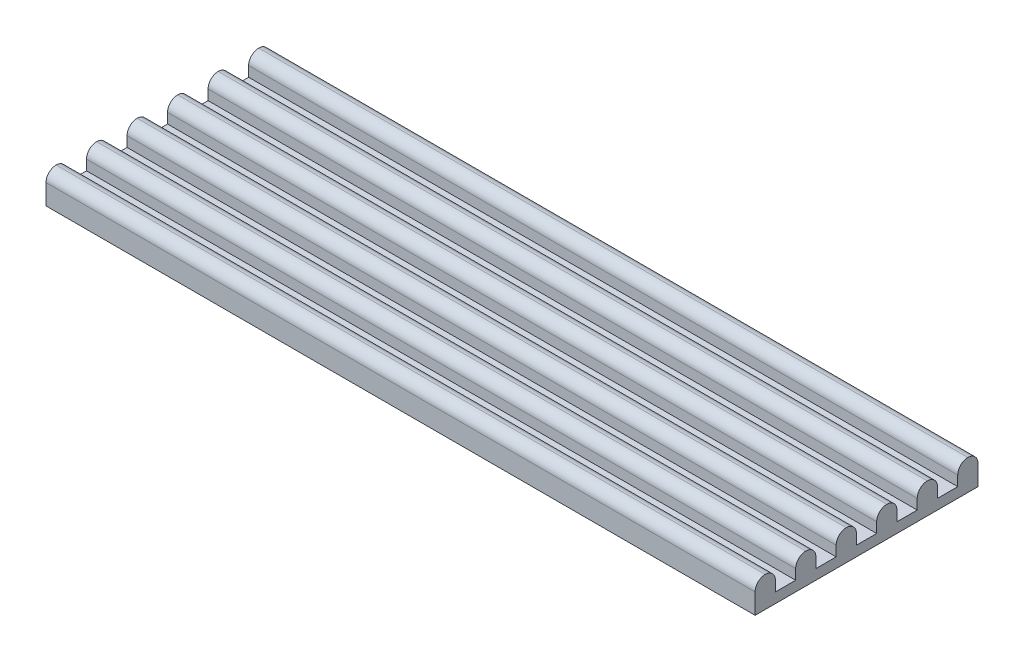
SolidWorks part; units mm, degrees
ref_plane "前视基准面" through (0, 0, 0) normal (0, 0, 1) x (1, 0, 0)
ref_plane "上视基准面" through (0, 0, 0) normal (0, 1, 0) x (1, 0, 0)
ref_plane "右视基准面" through (0, 0, 0) normal (1, 0, 0) x (0, 0, -1)
other "Configuration Table"
sketch "草图1" plane through (0, 0, 0) normal (0, 1, 0) x (1, 0, 0)
  line L1 (-35, 11) -> (35, 11)
  line L2 (-35, 11) -> (-35, -11)
  line L3 (-35, -11) -> (35, -11)
  line L4 (35, 11) -> (35, -11)
  line L5 (-35, 11) -> (35, -11) construction
  line L6 (-35, -11) -> (35, 11) construction
  point P0 (0, 0)
  dimension "D1" = 70
  dimension "D2" = 22
extrude "凸台-拉伸1" add sketch "草图1" along normal blind 3
sketch "草图2" plane through (0, 3, 0) normal (0, 1, 0) x (1, 0, 0)
  line L0 (-35, -9) -> (35, -9)
  line L1 (0, 15.35) -> (0, -16.9849) construction
  line L2 (-35, -7) -> (35, -7)
  line L3 (-35, -5) -> (35, -5)
  line L4 (35, 11) -> (-35, 11)
  line L5 (35, -11) -> (35, 11)
  line L6 (-35, -11) -> (35, -11)
  line L7 (-35, 11) -> (-35, -11)
  line L8 (35, 11) -> (-35, 11)
  line L9 (35, -11) -> (35, 11)
  line L10 (-35, -11) -> (35, -11)
  line L11 (-35, 11) -> (-35, -11)
  line L12 (-35, -3) -> (35, -3)
  line L13 (-35, -1) -> (35, -1)
  line L14 (-35, 1) -> (35, 1)
  line L15 (-35, 3) -> (35, 3)
  line L16 (-35, 5) -> (35, 5)
  line L17 (-35, 7) -> (35, 7)
  line L18 (-35, 9) -> (35, 9)
  line M11 (35, -11) -> (35, 11)
  line M13 (-35, 11) -> (-35, -11)
  dimension "D2" = 2
  dimension "D3" = 10
  dimension "D1" = 0
extrude "切除-拉伸1" cut sketch "草图2" against normal blind 2 contours L2 L1 L0 M11 | L1 L2 L0 M13 | L1 L12 L11 L3 | L12 L1 L3 M11 | L14 L1 L13 M11 | L1 L14 L11 L13 | L1 L16 L11 L15 | L16 L1 L15 M11 | L18 L1 L17 M11 | L1 L18 L11 L17 region at (-17.5, 3, 8) region at (17.5, 3, 8) region at (-17.5, 3, 4) region at (17.5, 3, 4) region at (-17.5, 3, 0) region at (17.5, 3, 0) region at (-17.5, 3, -4) region at (17.5, 3, -4) region at (-17.5, 3, -8) region at (17.5, 3, -8)
fillet "圆角1" radius 1 12 edges at (0, 3, 11) (0, 3, 9) (0, 3, 7) (0, 3, 5) (0, 3, 3) (0, 3, 1) (0, 3, -1) (0, 3, -3) (0, 3, -5) (0, 3, -7) (0, 3, -9) (0, 3, -11)
